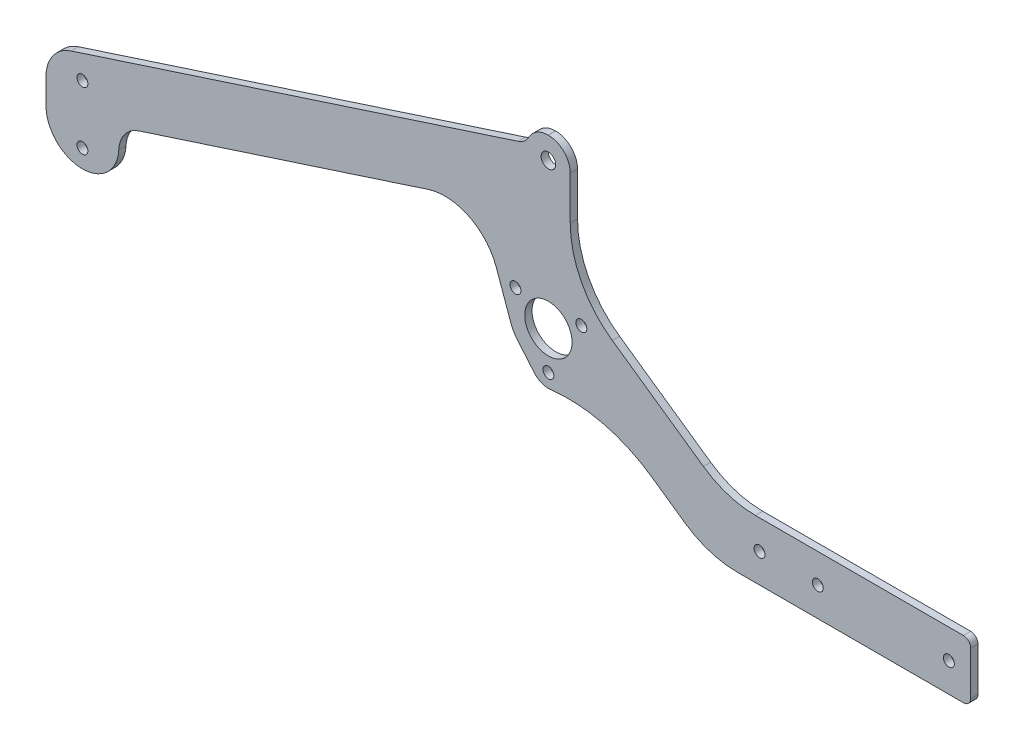
SolidWorks part; units mm, degrees
ref_plane "Спереди" through (0, 0, 0) normal (0, 0, 1) x (1, 0, 0)
ref_plane "Сверху" through (0, 0, 0) normal (0, 1, 0) x (1, 0, 0)
ref_plane "Справа" through (0, 0, 0) normal (1, 0, 0) x (0, 0, -1)
sketch "Эскиз Морковки" plane through (0, 0, 0) normal (0, 0, 1) x (1, 0, 0)
  line L0 (92, -110) -> (92, -24) construction
  line L1 (-53, -110) -> (-53, -24) construction
  line L2 (-198, -24) -> (-164, -24) construction
  line L3 (-198, -110) -> (-53, -110) construction
  line L4 (-198, -24) -> (-216, -24) construction
  line L5 (-53, -110) -> (92, -110) construction
  line L6 (-198, -110) -> (-198, -24) construction
  line L7 (58, -24) -> (92, -24) construction
  line L8 (110, -24) -> (92, -24) construction
  line L9 (-255.5, -110) -> (149.5, -110) construction
  line L10 (-198, -24) -> (-128, -24) construction
  line L11 (-128, -24) -> (-53, -24) construction
  line L12 (-128, -24) -> (0, 0) construction
  line L13 (0, 0) -> (92, -24) construction
  line L14 (-128, -24) -> (-128, -5) construction
  circle A0 centre (-198, -110) radius 57.5 construction
  circle A1 centre (-53, -110) radius 57.5 construction
  circle A2 centre (92, -110) radius 57.5 construction
  circle A3 centre (-216, -24) radius 1.5 construction
  circle A4 centre (-164, -24) radius 1.5 construction
  circle A5 centre (58, -24) radius 1.5 construction
  circle A6 centre (110, -24) radius 1.5 construction
  circle A7 centre (-87, -24) radius 1.5 construction
  circle A8 centre (-35, -24) radius 1.5 construction
  circle A9 centre (-128, -5) radius 1.5
  circle A10 centre (-128, -21) radius 1.5
  circle A11 centre (-128, -36) radius 2
  circle A12 centre (0, 40) radius 2
  circle A13 centre (-180, -24) radius 1.5
  circle A14 centre (74, -24) radius 1.5
  circle A15 centre (-71, -24) radius 1.5
  circle A16 centre (-61, -24) radius 1.5
  circle A17 centre (-45, -24) radius 1.5
  point P31 (-181, -24)
  dimension "D1" = 115
  dimension "D4" = 3
  dimension "D7" = 34
  dimension "D12" = 3
  dimension "D11" = 4
  dimension "D17" = 4
  dimension "D19" = 18
  dimension "D20" = 18
  dimension "D21" = 18
  dimension "D23" = 8
  dimension "D2" = 145
  dimension "D3" = 86
  dimension "D5" = 18
  dimension "D6" = 34
  dimension "D8" = 70
  dimension "D9" = 145
  dimension "D10" = 53
  dimension "D13" = 16
  dimension "D14" = 12
  dimension "D15" = 110
  dimension "D16" = 15
  dimension "D18" = 40
  dimension "D22" = 18
  dimension "D24" = 8
sketch "эскиз 1" plane through (0, 0, 0) normal (0, 0, 1) x (1, 0, 0)
  line L0 (-222, -16) -> (-222, -32)
  line L1 (-222, -32) -> (-152, -32)
  line L2 (-152, -32) -> (-152, -47)
  line L3 (-222, -16) -> (-144.1949, -16)
  line L4 (-53, -110) -> (92, -110) construction
  line L5 (-29, -32) -> (-29, -16)
  line L6 (-152, -47) -> (-104, -47)
  line L9 (-134.245, -27) -> (-121.755, -27)
  line L10 (-104, -32) -> (-104, -47)
  line L11 (-53, -16) -> (-53, -110) construction
  line L12 (-104, -32) -> (-29, -32)
  line L13 (-29, -32) -> (-104, -32)
  line L14 (-138, -26) -> (-118, -26) construction
  line L15 (-111.8051, -16) -> (-29, -16)
  line L16 (-128, -24) -> (-128, -5) construction
  line L17 (-53, -110) -> (-53, -24) construction
  line L18 (-198, -16) -> (-198, -32) construction
  line L19 (-198, -110) -> (-198, -24) construction
  line L20 (-198, -24) -> (-216, -24) construction
  line L21 (-128, -27) -> (-128, -47) construction
  line L22 (-138, -27) -> (-138, -16) construction
  line L23 (-118, -26.2682) -> (-118, -16) construction
  line L24 (-144.1949, -16) -> (-144.1949, -27) construction
  line L25 (-144.1949, -27) -> (-111.8051, -27) construction
  line L26 (-111.8051, -27) -> (-111.8051, -16) construction
  circle A0 centre (-216, -24) radius 1.5
  circle A1 centre (-164, -24) radius 1.5
  circle A2 centre (-128, -36) radius 2
  circle A3 centre (-87, -24) radius 1.5
  circle A4 centre (-35, -24) radius 1.5
  circle A5 centre (-35, -24) radius 1.5 construction
  circle A6 centre (-87, -24) radius 1.5 construction
  circle A7 centre (-128, -36) radius 2 construction
  circle A8 centre (-164, -24) radius 1.5 construction
  circle A9 centre (-216, -24) radius 1.5 construction
  circle A10 centre (-128, -16) radius 10 construction
  circle A11 centre (-128, -36) radius 20 construction
  arc A12 (-121.755, -27) -> (-111.8051, -16) centre (-121.755, -17) ccw
  arc A13 (-134.245, -27) -> (-144.1949, -16) centre (-134.245, -17) cw
  circle A14 centre (-180, -24) radius 1.5
  circle A15 centre (-180, -24) radius 1.5 construction
  circle A16 centre (-71, -24) radius 1.5
  circle A17 centre (-71, -24) radius 1.5 construction
  point P25 (-128, -47)
  dimension "D6" = 9
  dimension "D5" = 20
  dimension "D1" = 24
  dimension "D2" = 24
  dimension "D3" = 16
  dimension "D4" = 11
  dimension "D7" = 70
  dimension "D8" = 8
  dimension "D9" = 5
extrude "тело маленькой арки" [suppressed] add sketch "эскиз 1" along normal blind 2
fillet "Скругление2" [suppressed] radius 10
fillet "Скругление3" [suppressed] radius 15
fillet "Скругление16" [suppressed] radius 8
fillet "Скругление18" [suppressed] radius 2
sketch "Эскиз1" plane through (0, 0, 0) normal (0, 0, 1) x (1, 0, 0)
  line L0 (6, 14.0315) -> (49.0312, -16)
  line L1 (49.0312, -16) -> (116, -16)
  line L2 (116, -16) -> (116, -32)
  line L3 (116, -32) -> (44, -32)
  line L4 (44, -32) -> (8.372, -7.1351)
  line L5 (-12.7222, 2.951) -> (-10.3652, -3.6828) construction
  line L6 (-10.3652, -3.6828) -> (-19.1717, 21.1032)
  line L7 (6, 14.0315) -> (6, 46)
  line L8 (-131.0902, 0.5106) -> (-6, 41.1548)
  line L9 (-138, -16) -> (-138, -9)
  line L10 (52, -16) -> (52, -32) construction
  line L11 (-118, -11.0081) -> (-19.1717, 21.1032)
  line L12 (-8.9167, 9.5422) -> (-1.9932, 10.8179) construction
  line L13 (92, -110) -> (92, -24) construction
  line L14 (3.8054, -12.4932) -> (8.372, -7.1351)
  line L15 (-3.8054, -12.4932) -> (-8.372, -7.1351)
  line L16 (-138, -26) -> (-118, -26) construction
  line L17 (-118, -16) -> (-118, -11.0081)
  line L18 (-128, -5) -> (-128, -26) construction
  line L19 (-128, -24) -> (-128, -5) construction
  line L20 (8.9167, 9.5422) -> (1.9932, 10.8179) construction
  line L21 (-118, -26) -> (-118, -16) construction
  line L22 (6, 46) -> (-6, 46)
  line L23 (-138, 1) -> (-118, 1) construction
  line L24 (-6, 46) -> (-6, 41.1548)
  line L27 (12.7222, 2.951) -> (10.3652, -3.6828) construction
  line L31 (-138, -16) -> (-138, -26) construction
  line L32 (-12.7222, 2.951) -> (-10.3652, -3.6828) [skipped]
  circle A0 centre (-128, -21) radius 1.5
  circle A1 centre (-128, -5) radius 1.5
  circle A2 centre (-128, -5) radius 1.5 construction
  circle A3 centre (-128, -21) radius 1.5 construction
  circle A4 centre (0, 0) radius 6.5
  circle A5 centre (0, 0) radius 11 construction
  arc A6 (-8.9167, 9.5422) -> (-12.7222, 2.951) centre (-8.0107, 4.625) ccw construction
  arc A7 (1.9932, 10.8179) -> (-1.9932, 10.8179) centre (0, 0) ccw construction
  arc A8 (-3.8054, -12.4932) -> (3.8054, -12.4932) centre (0, -9.25) ccw
  arc A9 (12.7222, 2.951) -> (8.9167, 9.5422) centre (8.0107, 4.625) ccw construction
  arc A10 (8.372, -7.1351) -> (10.3652, -3.6828) centre (0, 0) ccw construction
  arc A11 (-8.372, -7.1351) -> (-10.3652, -3.6828) centre (0, 0) cw
  circle A12 centre (0, 0) radius 9.25 construction
  circle A13 centre (0, -10.45) radius 1.5
  circle A14 centre (-9.05, 5.225) radius 1.5
  circle A15 centre (9.05, 5.225) radius 1.5
  circle A16 centre (0, 0) radius 7.65 construction
  circle A17 centre (110, -24) radius 1.5
  circle A18 centre (58, -24) radius 1.5
  circle A19 centre (58, -24) radius 1.5 construction
  circle A20 centre (110, -24) radius 1.5 construction
  circle A21 centre (0, 40) radius 2
  circle A22 centre (0, 40) radius 2 construction
  arc A23 (-138, -16) -> (-118, -16) centre (-128, -16) ccw
  arc A24 (-131.0902, 0.5106) -> (-138, -9) centre (-128, -9) ccw
  circle A25 centre (52, -6.5586) radius 25.4414 construction
  circle A26 centre (74, -24) radius 1.5
  circle A27 centre (74, -24) radius 1.5 construction
  point P27 (116, -24)
  point P33 (0, 46)
  point P62 (0, 0)
  point P68 (0, 0)
  dimension "D2" = 13
  dimension "D3" = 3
  dimension "D5" = 5
  dimension "D6" = 18.5
  dimension "D7" = 22
  dimension "D14" = 3
  dimension "D17" = 15.3
  dimension "D18" = 6
  dimension "D20" = 12
  dimension "D13" = 6
  dimension "D22" = 20
  dimension "D4" = 18
  dimension "D11" = 6
  dimension "D16" = 16
  dimension "D9" = 8
  dimension "D1" = 16
  dimension "D8" = 10
  dimension "D10" = 24
  dimension "D12" = 15
  dimension "D15" = 3
  dimension "D19" = 10.45
  dimension "D21" = 5
extrude "тело большой арки" add sketch "Эскиз1" along normal blind 2
fillet "Скругление7" radius 15 1 edges at (-19.1717, 21.1032, 1)
fillet "Скругление8" radius 40 1 edges at (8.372, -7.1351, 1)
fillet "Скругление20" radius 6 2 edges at (6, 46, 1) (-6, 46, 1)
fillet "Скругление10" radius 27 1 edges at (6, 14.0315, 1)
fillet "Скругление17" radius 8 1 edges at (-118, -11.0081, 1)
fillet "Скругление21" radius 5 1 edges at (-6, 41.1548, 1)
fillet "Скругление23" radius 2 2 edges at (116, -32, 1) (116, -16, 1)
fillet "Скругление25" radius 25 2 edges at (49.0312, -16, 1) (44, -32, 1)
